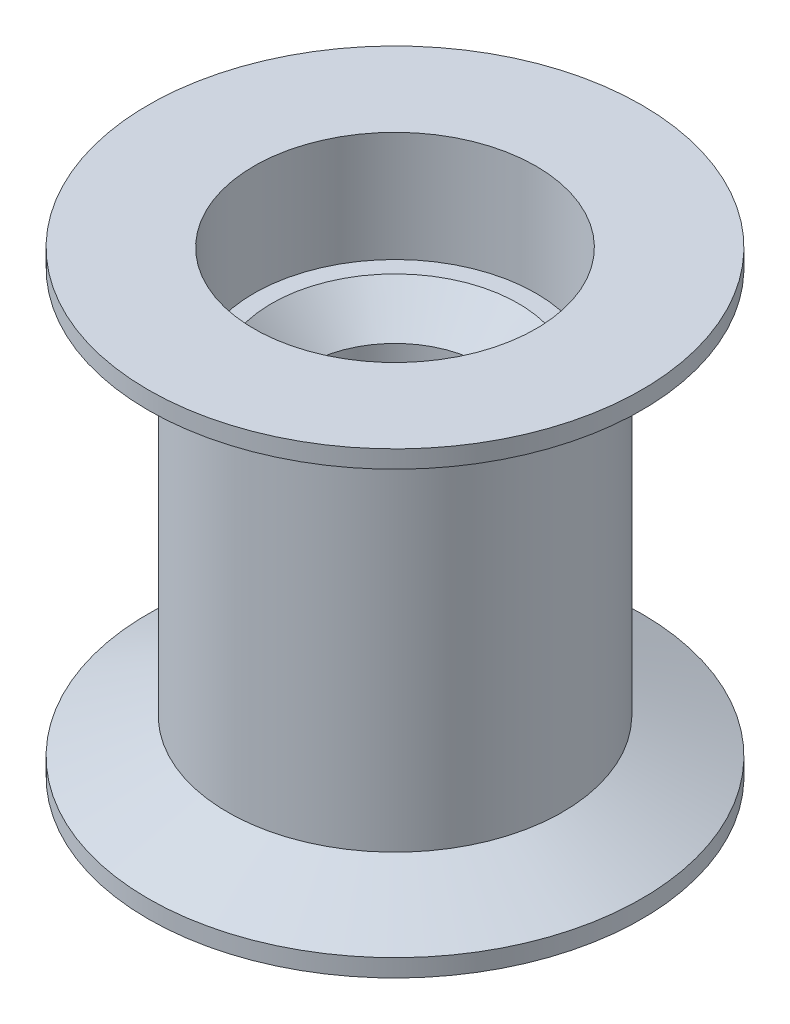
SolidWorks part; units mm, degrees
material "Markforged"
ref_plane "Front Plane" through (0, 0, 0) normal (0, 0, 1) x (1, 0, 0)
ref_plane "Top Plane" through (0, 0, 0) normal (0, 1, 0) x (1, 0, 0)
ref_plane "Right Plane" through (0, 0, 0) normal (1, 0, 0) x (0, 0, -1)
other "Bounding Box"
ref_plane "Default Plane" through (-8.9266, -12.7485, 0) normal (-0.1736, 0.9848, 0) x (0.9848, 0.1736, 0)
sketch "Sketch2" plane through (0, 0, 0) normal (1, 0, 0) x (0, 0, -1)
  line L0 (0, 0) -> (196218.8196, 0) construction
  line L1 (0, 0) -> (0, 196218.8196) construction
  line L2 (2.5, 0) -> (2.5, 3.375)
  line L3 (2.5, 3.375) -> (4, 3.375)
  line L4 (4, 3.375) -> (4, 6.5)
  line L5 (4, 6.5) -> (7, 6.5)
  line L6 (7, 6.5) -> (7, 6)
  line L7 (7, 6) -> (4.75, 5)
  line L8 (4.75, 5) -> (4.75, 0)
  line L9 (4.75, 0) -> (2.5, 0)
  dimension "D1" = 5
  dimension "D2" = 8
  dimension "D3" = 3.125
  dimension "D4" = 9.5
  dimension "D5" = 14
  dimension "D6" = 10
  dimension "D7" = 0.5
  dimension "D8" = 1.5
revolve "Revolve1" add sketch "Sketch2" angle 360 about L1
mirror "Mirror1" about plane through (0, 0, 0) normal (0, 1, 0) of "Revolve1"
chamfer "Chamfer1" distance 1 angle 45 2 edges at (0, -3.375, -2.5) (0, 3.375, -2.5)
